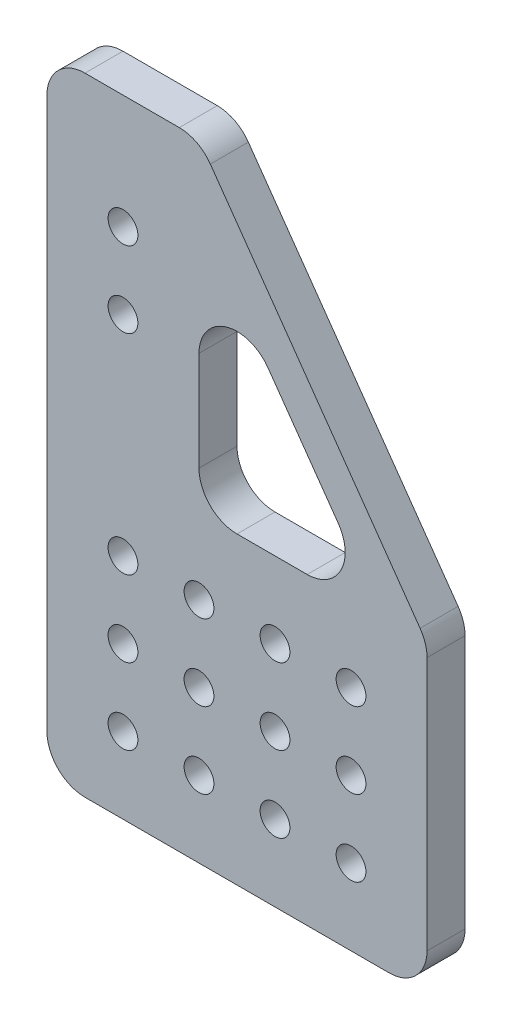
SolidWorks part; units mm, degrees
material "6061-T6 (SS)"
ref_plane "Front Plane" through (0, 0, 0) normal (0, 0, 1) x (1, 0, 0)
ref_plane "Top Plane" through (0, 0, 0) normal (0, 1, 0) x (1, 0, 0)
ref_plane "Right Plane" through (0, 0, 0) normal (1, 0, 0) x (0, 0, -1)
sketch "Sketch1" plane through (0, 0, 0) normal (0, 0, 1) x (1, 0, 0)
  line L0 (0, 0) -> (0, 104.775)
  line L1 (0, 104.775) -> (25.4, 104.775)
  line L2 (25.4, 104.775) -> (63.5, 50.8)
  line L3 (63.5, 50.8) -> (63.5, 0)
  line L4 (63.5, 0) -> (0, 0)
  circle A0 centre (12.7, 85.725) radius 2.4892
  circle A1 centre (12.7, 73.025) radius 2.4892
  circle A2 centre (12.7, 12.7) radius 2.4892
  point P12 (0, 0)
  dimension "D8" = 12.7
  dimension "D9" = 4.9784
  dimension "D1" = 104.775
  dimension "D2" = 25.4
  dimension "D3" = 63.5
  dimension "D4" = 50.8
  dimension "D5" = 12.7
  dimension "D6" = 12.7
  dimension "D7" = 19.05
extrude "Boss-Extrude1" add sketch "Sketch1" along normal mid plane 6.35
pattern_linear "LPattern1" count 4 spacing 12.7 along (1, 0, 0) count 3 spacing 12.7 along (0, 1, 0) of face at (15.1892, 12.7, 3.175)
sketch "Sketch2" plane through (0, 0, 3.175) normal (0, 0, 1) x (1, 0, 0)
  line L1 (25.4, 93.7638) -> (25.4, 50.8)
  line L2 (0, 104.775) -> (0, 0) construction
  line L3 (55.7274, 50.8) -> (25.4, 93.7638)
  line L4 (25.4, 50.8) -> (55.7274, 50.8)
  line L5 (0, 0) -> (63.5, 0) construction
  line L6 (63.5, 50.8) -> (25.4, 104.775) construction
  dimension "D1" = 25.4
  dimension "D2" = 50.8
  dimension "D3" = 6.35
extrude "Cut-Extrude1" cut sketch "Sketch2" against normal through all
fillet "Fillet1" radius 6.35 8 edges at (0, 0, 0) (25.4, 104.775, 0) (63.5, 50.8, 0) (63.5, 0, 0) (0, 104.775, 0) (25.4, 93.7638, 0) (55.7274, 50.8, 0) (25.4, 50.8, 0)
